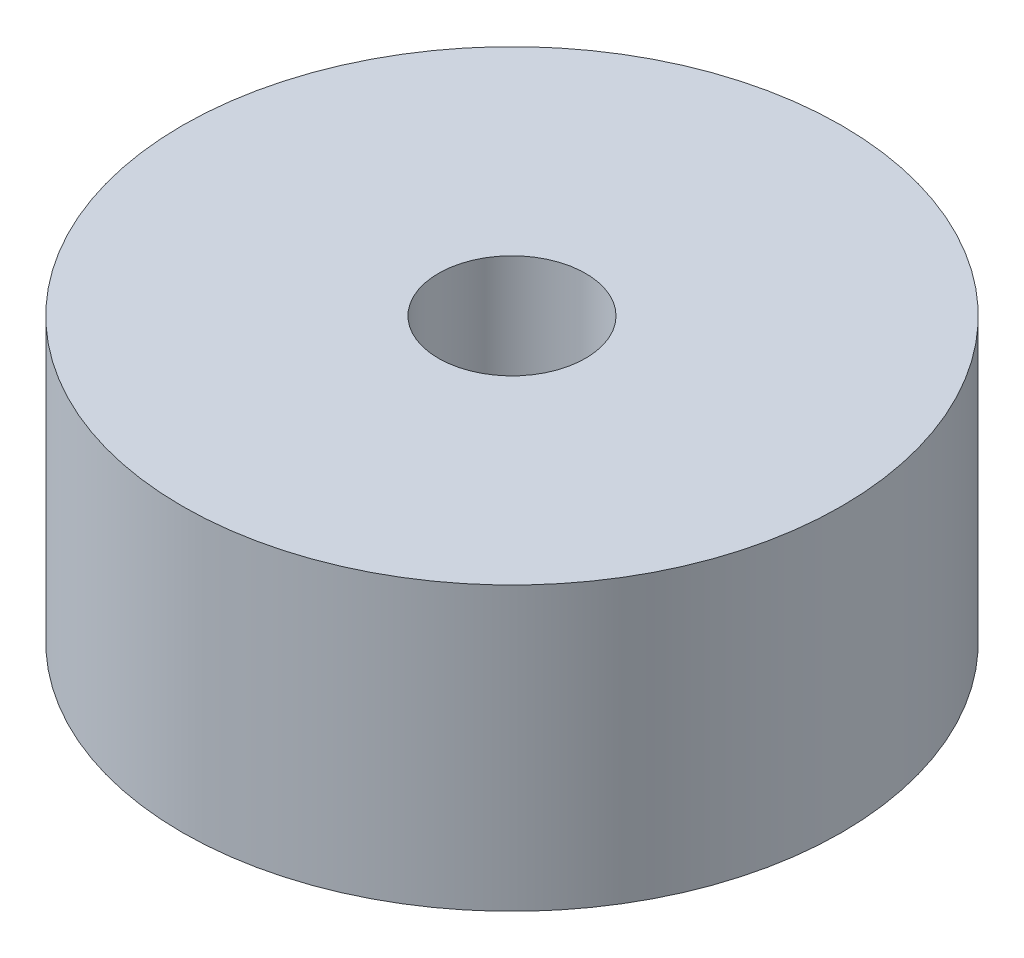
SolidWorks part; units mm, degrees
ref_plane "前视基准面" through (0, 0, 0) normal (0, 0, 1) x (1, 0, 0)
ref_plane "上视基准面" through (0, 0, 0) normal (0, 1, 0) x (1, 0, 0)
ref_plane "右视基准面" through (0, 0, 0) normal (1, 0, 0) x (0, 0, -1)
other "Configuration Table"
sketch "草图1" plane through (0, 0, 0) normal (0, 1, 0) x (1, 0, 0)
  circle A0 centre (0, 0) radius 5.6
  circle A1 centre (0, 0) radius 1.25
  dimension "D1" = 2.5
  dimension "D2" = 11.2
extrude "凸台-拉伸1" add sketch "草图1" along normal blind 4.8 contours A0 | A1
